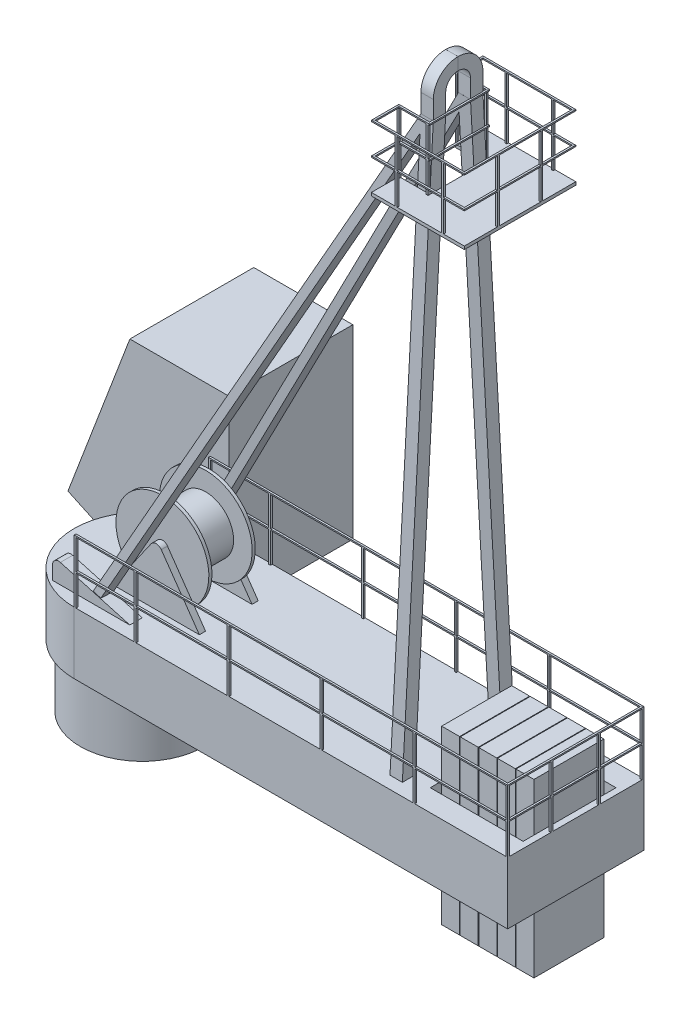
SolidWorks part; units mm, degrees
ref_plane "Front Plane" through (0, 0, 0) normal (0, 0, 1) x (1, 0, 0)
ref_plane "Top Plane" through (0, 0, 0) normal (0, 1, 0) x (1, 0, 0)
ref_plane "Right Plane" through (0, 0, 0) normal (1, 0, 0) x (0, 0, -1)
sketch "Sketch1" plane through (0, 0, 0) normal (0, 1, 0) x (1, 0, 0)
  circle A0 centre (0, 0) radius 1000
  dimension "D1" = 2000
extrude "Boss-Extrude1" add sketch "Sketch1" along normal blind 1000
sketch "Sketch2" plane through (0, 1000, 0) normal (0, 1, 0) x (1, 0, 0)
  line L1 (7000, -1100) -> (0, -1100)
  line L2 (7000, -1100) -> (7000, 1100)
  line L3 (7000, 1100) -> (0, 1100)
  line L5 (5400, -750) -> (6900, -750)
  line L6 (5400, -750) -> (5400, 750)
  line L7 (5400, 750) -> (6900, 750)
  line L8 (6900, -750) -> (6900, 750)
  line L9 (5400, -750) -> (6900, 750) construction
  line L10 (5400, 750) -> (6900, -750) construction
  circle A2 centre (0, 0) radius 1100
  arc A3 (0, 1100) -> (0, -1100) centre (0, 0) ccw
  point P0 (1484.5007, 0)
  point P6 (6150, 0)
  dimension "D2" = 7000
  dimension "D3" = 7000
  dimension "D4" = 1500
  dimension "D5" = 1500
  dimension "D6" = 100
extrude "Boss-Extrude2" add sketch "Sketch2" along normal blind 1000
sketch "Sketch3" plane through (5400, 0, 0) normal (1, 0, 0) x (0, 0, -1)
  line L1 (-565.5574, -8.1645) -> (565.5574, -8.1645)
  line L2 (-565.5574, -8.1645) -> (-565.5574, 2768.8659)
  line L3 (-565.5574, 2768.8659) -> (565.5574, 2768.8659)
  line L4 (565.5574, -8.1645) -> (565.5574, 2768.8659)
  line L5 (-565.5574, -8.1645) -> (565.5574, 2768.8659) construction
  line L6 (-565.5574, 2768.8659) -> (565.5574, -8.1645) construction
  point P0 (0, 1380.3507)
extrude "Boss-Extrude3" add sketch "Sketch3" along normal blind 290 separate body
pattern_linear "LPattern1" count 5 spacing 300 along (1, 0, 0) of "Boss-Extrude3"
ref_plane "Plane1" through (4900, 0, 0) normal (1, 0, 0) x (0, 0, -1)
sketch "Sketch4" plane through (4900, 0, 0) normal (1, 0, 0) x (0, 0, -1)
  line L0 (-900, 2000) -> (-400.308, 11000)
  line L1 (-400.308, 11000) -> (-200, 11000)
  line L2 (-200, 11000) -> (-699.692, 2000)
  line L3 (-1100, 2000) -> (1100, 2000) construction
  line L4 (-699.692, 2000) -> (-900, 2000)
  line L5 (-400.308, 11000) -> (-400.308, 11300)
  line L6 (-200.308, 11000) -> (-200.308, 11300)
  line L7 (-0.157, 11700.151) -> (-0.157, 11500.151)
  line L8 (-1100, 2000) -> (-1100, 1000) construction
  arc A0 (-400.308, 11300) -> (-0.157, 11700.151) centre (-0.157, 11300) cw
  arc A1 (-200.308, 11300) -> (-0.157, 11500.151) centre (-0.157, 11300) cw
  dimension "D1" = 9000
  dimension "D2" = 200
  dimension "D3" = 200
  dimension "D5" = 300
  dimension "D6" = 200
  dimension "D4" = 200
extrude "Boss-Extrude4" add sketch "Sketch4" along normal blind 200 contours L6 A1 L7 A0 L5 L1 | L4 L2 L1 L0 region at (4900, 6500, 550) region at (4900, 11362.768, 237.9729)
ref_plane "Plane2" through (0, 55.9619, 1007.9356) normal (0, 0.0554, 0.9985) x (1, 0, 0)
sketch "Sketch5" plane through (0, 55.9619, 1007.9356) normal (0, 0.0554, 0.9985) x (1, 0, 0)
  line L0 (0, 1935.9449) -> (4900, 10960.8932)
  line L1 (4900, 10960.8932) -> (4900, 10693.5077)
  line L2 (4900, 10693.5077) -> (145.1742, 1935.9449)
  line L3 (145.1742, 1935.9449) -> (0, 1935.9449)
  line L15 (0, 1935.9449) -> (0, 937.4827) construction
  line L18 (0, 1935.9449) -> (7000, 1935.9449) construction
  line L19 (4900, 1947.0321) -> (4900, 10960.8932) construction
extrude "Boss-Extrude6" add sketch "Sketch5" against normal blind 200
ref_plane "Plane3" through (0, 2800, 0) normal (0, 1, 0) x (1, 0, 0)
sketch "Sketch6" plane through (0, 2800, 0) normal (0, 1, 0) x (1, 0, 0)
  line L0 (700, 375) -> (700, -375)
  line L1 (700, -375) -> (1450, -375)
  line L2 (1450, -375) -> (1450, -325)
  line L3 (1450, -325) -> (1150, -325)
  line L4 (1150, -325) -> (1150, 325)
  line L5 (1150, 325) -> (1450, 325)
  line L6 (1450, 325) -> (1450, 375)
  line L7 (1450, 375) -> (700, 375)
  point P2 (700, 0)
  dimension "D1" = 700
  dimension "D2" = 750
  dimension "D3" = 750
  dimension "D4" = 300
  dimension "D5" = 750
  dimension "D6" = 50
  dimension "D7" = 50
revolve "Revolve1" add sketch "Sketch6" angle 360 about L0
sketch "Sketch7" plane through (0, 0, 375) normal (0, 0, 1) x (1, 0, 0)
  line L0 (0, 2000) -> (617.8994, 2882.7134)
  line L1 (781.8621, 2882.5469) -> (1396.9772, 2000)
  line L2 (0, 2000) -> (7000, 2000) construction
  line L3 (0, 2000) -> (1396.9772, 2000)
  arc A1 (781.8621, 2882.5469) -> (617.8994, 2882.7134) centre (699.8226, 2825.3672) ccw
  point P12 (700, 3000)
  dimension "D2" = 1218.9246
  dimension "D3" = 100
  dimension "D1" = 1000
extrude "Boss-Extrude7" add sketch "Sketch7" along normal blind 100
ref_plane "Plane4" through (0, 0, 900) normal (0, 0, 1) x (1, 0, 0)
sketch "Sketch8" plane through (0, 0, 900) normal (0, 0, 1) x (1, 0, 0)
  line L0 (-550, 2000) -> (-550, 2218.1109)
  line L1 (0, 2000) -> (-1100, 2000) construction
  line L2 (-423.0067, 2314.3988) -> (698.4886, 2000)
  line L3 (0, 2000) -> (1396.9772, 2000) construction
  line L4 (-550, 2000) -> (698.4886, 2000)
  arc A0 (-423.0067, 2314.3988) -> (-550, 2218.1109) centre (-450, 2218.1109) ccw
  point P10 (-550, 2350)
  dimension "D2" = 100
  dimension "D1" = 350
extrude "Boss-Extrude8" add sketch "Sketch8" against normal blind 200
mirror "Mirror1" about plane through (0, 0, 0) normal (0, 0, 1) of "Boss-Extrude8", "Boss-Extrude6", "Boss-Extrude4", "Boss-Extrude7"
ref_plane "Plane5" through (0, 10000, 0) normal (0, 1, 0) x (1, 0, 0)
sketch "Sketch9" plane through (0, 10000, 0) normal (0, 1, 0) x (1, 0, 0)
  line L0 (5100, -455.8294) -> (4600, -455.8294)
  line L2 (4600, -455.8294) -> (4600, -900)
  line L3 (-1210, -900) -> (1210, -900) construction
  line L4 (4600, -900) -> (6100, -900)
  line L5 (6100, -900) -> (6100, 900)
  line L6 (6100, 900) -> (4600, 900)
  line L7 (4600, 900) -> (4600, 455.8294)
  line L8 (4600, 455.8294) -> (5100, 455.8294)
  line L10 (5100, 455.8294) -> (5100, -455.8294)
  dimension "D1" = 1000
  dimension "D2" = 500
  dimension "D3" = 500
extrude "Boss-Extrude9" add sketch "Sketch9" against normal blind 50
sketch "Sketch10" plane through (0, 10000, 0) normal (0, 1, 0) x (1, 0, 0)
  line L0 (6100, -900) -> (6100, 900) construction
  line L1 (6070, -365) -> (6100, -365)
  line L2 (6070, -365) -> (6070, -335)
  line L3 (6070, -335) -> (6100, -335)
  line L4 (6100, -365) -> (6100, -335)
  line L5 (6070, -365) -> (6100, -335) construction
  line L6 (6070, -335) -> (6100, -365) construction
  line L7 (4600, -900) -> (6100, -900) construction
  line L8 (5765, -870) -> (5735, -870)
  line L9 (5765, -870) -> (5765, -900)
  line L10 (5765, -900) -> (5735, -900)
  line L11 (5735, -870) -> (5735, -900)
  line L12 (5765, -870) -> (5735, -900) construction
  line L13 (5765, -900) -> (5735, -870) construction
  line L19 (-4455, 0) -> (4455, 0) construction
  line L20 (5015, -870) -> (4985, -870)
  line L21 (5015, -870) -> (5015, -900)
  line L22 (5015, -900) -> (4985, -900)
  line L23 (4985, -870) -> (4985, -900)
  line L24 (5015, -870) -> (4985, -900) construction
  line L25 (5015, -900) -> (4985, -870) construction
  line L26 (5015, 900) -> (4985, 870) construction
  line L27 (5015, 870) -> (4985, 900) construction
  line L28 (5765, 900) -> (5735, 870) construction
  line L29 (5765, 870) -> (5735, 900) construction
  line L30 (6070, 335) -> (6100, 365) construction
  line L31 (6070, 365) -> (6100, 335) construction
  line L32 (4985, 870) -> (4985, 900)
  line L33 (5015, 900) -> (4985, 900)
  line L34 (5015, 870) -> (5015, 900)
  line L35 (5015, 870) -> (4985, 870)
  line L36 (5735, 870) -> (5735, 900)
  line L37 (5765, 900) -> (5735, 900)
  line L38 (5765, 870) -> (5765, 900)
  line L39 (5765, 870) -> (5735, 870)
  line L40 (6100, 365) -> (6100, 335)
  line L41 (6070, 335) -> (6100, 335)
  line L42 (6070, 365) -> (6070, 335)
  line L43 (6070, 365) -> (6100, 365)
  line L44 (5070, 455.8294) -> (5100, 485.8294) construction
  line L45 (4630, -485.8294) -> (4600, -485.8294)
  line L46 (4630, -485.8294) -> (4630, -455.8294)
  line L47 (4630, -455.8294) -> (4600, -455.8294)
  line L48 (4600, -485.8294) -> (4600, -455.8294)
  line L49 (4630, -485.8294) -> (4600, -455.8294) construction
  line L50 (4630, -455.8294) -> (4600, -485.8294) construction
  line L51 (5070, -485.8294) -> (5100, -485.8294)
  line L52 (5070, -485.8294) -> (5070, -455.8294)
  line L53 (5070, -455.8294) -> (5100, -455.8294)
  line L54 (5100, -485.8294) -> (5100, -455.8294)
  line L55 (5070, -485.8294) -> (5100, -455.8294) construction
  line L56 (5070, -455.8294) -> (5100, -485.8294) construction
  line L57 (5070, 485.8294) -> (5100, 455.8294) construction
  line L58 (4630, 455.8294) -> (4600, 485.8294) construction
  line L59 (4630, 485.8294) -> (4600, 455.8294) construction
  line L60 (5100, 485.8294) -> (5100, 455.8294)
  line L61 (5070, 455.8294) -> (5100, 455.8294)
  line L62 (5070, 485.8294) -> (5070, 455.8294)
  line L63 (5070, 485.8294) -> (5100, 485.8294)
  line L64 (4600, 485.8294) -> (4600, 455.8294)
  line L65 (4630, 455.8294) -> (4600, 455.8294)
  line L66 (4630, 485.8294) -> (4630, 455.8294)
  line L67 (4630, 485.8294) -> (4600, 485.8294)
  point P0 (6085, -350)
  point P7 (5750, -885)
  point P14 (5000, -885)
  point P34 (5000, 885)
  point P35 (5750, 885)
  point P36 (6085, 350)
  point P37 (4615, -470.8294)
  point P43 (5085, -470.8294)
  point P57 (5085, 470.8294)
  point P58 (4615, 470.8294)
  dimension "D1" = 30
  dimension "D2" = 30
  dimension "D3" = 30
  dimension "D4" = 30
  dimension "D5" = 30
  dimension "D6" = 30
  dimension "D7" = 350
  dimension "D8" = 350
  dimension "D9" = 750
  dimension "D10" = 30
  dimension "D11" = 30
  dimension "D12" = 30
  dimension "D13" = 30
extrude "Boss-Extrude10" add sketch "Sketch10" along normal blind 1000
sketch "Sketch11" plane through (0, 11000, 0) normal (0, 1, 0) x (1, 0, 0)
  line L0 (5110, -470.8294) -> (4615, -470.8294)
  line L3 (4615, -470.8294) -> (4615, -885)
  line L5 (4615, -885) -> (6085, -885)
  line L6 (6085, -885) -> (6085, 885)
  line L7 (6085, 885) -> (4615, 885)
  line L8 (4615, 885) -> (4615, 470.8294)
  line L9 (4615, 470.8294) -> (5110, 470.8294)
  line L10 (5110, 470.8294) -> (5110, -470.8294)
  line L11 (4985, 900) -> (4985, 870) construction
  line L12 (4630, 485.8294) -> (4600, 485.8294) construction
  line L14 (5070, 485.8294) -> (5070, 455.8294) construction
  line L16 (4630, -485.8294) -> (4630, -455.8294) construction
  line L17 (4600, -485.8294) -> (4630, -485.8294) construction
  line L19 (5015, -900) -> (5015, -870) construction
  line L20 (6070, -365) -> (6100, -365) construction
  line L21 (5100, -485.8294) -> (5100, -455.8294) construction
  point P5 (4630, -470.8294)
  point P22 (4985, 885)
  point P26 (4615, 485.8294)
  point P29 (5070, 470.8294)
  point P32 (4615, -485.8294)
  point P33 (5015, -885)
  point P36 (6085, -365)
  dimension "D1" = 10
sketch "Sketch19" plane through (0, 0, 485.8294) normal (0, 0, 1) x (1, 0, 0)
  line L0 (4600, 11000) -> (4630, 11000) construction
  line L1 (4600, 11010) -> (4630, 11010)
  line L2 (4600, 11010) -> (4600, 10990)
  line L3 (4600, 10990) -> (4630, 10990)
  line L4 (4630, 11010) -> (4630, 10990)
  line L5 (4600, 11010) -> (4630, 10990) construction
  line L6 (4600, 10990) -> (4630, 11010) construction
  line L7 (4630, 11000) -> (4630, 10000) construction
  point P0 (4615, 11000)
  dimension "D1" = 20
sweep "Sweep3" add profiles "Sketch19" path "Sketch11"
sketch "Sketch20" plane through (0, 2000, 0) normal (0, 1, 0) x (1, 0, 0)
  line L0 (5470, -1070) -> (5470, -1100)
  line L1 (6970, -1070) -> (7000, -1070)
  line L2 (6970, -1070) -> (6970, -1100)
  line L3 (6970, -1100) -> (7000, -1100)
  line L4 (7000, -1070) -> (7000, -1100)
  line L5 (6970, -1070) -> (7000, -1100) construction
  line L6 (6970, -1100) -> (7000, -1070) construction
  line L7 (5470, -1070) -> (5500, -1070)
  line L8 (5500, -1070) -> (5500, -1100)
  line L9 (5470, -1100) -> (5500, -1100)
  line L10 (3970, -1070) -> (3970, -1100)
  line L11 (3970, -1070) -> (4000, -1070)
  line L12 (4000, -1070) -> (4000, -1100)
  line L13 (3970, -1100) -> (4000, -1100)
  line L14 (2470, -1070) -> (2470, -1100)
  line L15 (2470, -1070) -> (2500, -1070)
  line L16 (2500, -1070) -> (2500, -1100)
  line L17 (2470, -1100) -> (2500, -1100)
  line L18 (970, -1070) -> (970, -1100)
  line L19 (970, -1070) -> (1000, -1070)
  line L20 (1000, -1070) -> (1000, -1100)
  line L21 (970, -1100) -> (1000, -1100)
  line L22 (6970, -370) -> (6970, -400)
  line L23 (30, -1070) -> (0, -1070)
  line L24 (30, -1070) -> (30, -1100)
  line L25 (30, -1100) -> (0, -1100)
  line L26 (0, -1070) -> (0, -1100)
  line L27 (30, -1070) -> (0, -1100) construction
  line L28 (30, -1100) -> (0, -1070) construction
  line L29 (6970, -370) -> (7000, -370)
  line L30 (7000, -370) -> (7000, -400)
  line L31 (6970, -400) -> (7000, -400)
  line L33 (-4455, 0) -> (4455, 0) construction
  line L34 (30, 1100) -> (0, 1070) construction
  line L35 (30, 1070) -> (0, 1100) construction
  line L36 (6970, 1100) -> (7000, 1070) construction
  line L37 (6970, 1070) -> (7000, 1100) construction
  line L38 (6970, 400) -> (7000, 400)
  line L39 (7000, 370) -> (7000, 400)
  line L40 (6970, 370) -> (7000, 370)
  line L41 (0, 1070) -> (0, 1100)
  line L42 (30, 1100) -> (0, 1100)
  line L43 (30, 1070) -> (30, 1100)
  line L44 (30, 1070) -> (0, 1070)
  line L45 (6970, 370) -> (6970, 400)
  line L46 (970, 1100) -> (1000, 1100)
  line L47 (1000, 1070) -> (1000, 1100)
  line L48 (970, 1070) -> (1000, 1070)
  line L49 (970, 1070) -> (970, 1100)
  line L50 (2470, 1100) -> (2500, 1100)
  line L51 (2500, 1070) -> (2500, 1100)
  line L52 (2470, 1070) -> (2500, 1070)
  line L53 (2470, 1070) -> (2470, 1100)
  line L54 (3970, 1100) -> (4000, 1100)
  line L55 (4000, 1070) -> (4000, 1100)
  line L56 (3970, 1070) -> (4000, 1070)
  line L57 (3970, 1070) -> (3970, 1100)
  line L58 (5470, 1100) -> (5500, 1100)
  line L59 (5500, 1070) -> (5500, 1100)
  line L60 (5470, 1070) -> (5500, 1070)
  line L61 (5470, 1070) -> (5470, 1100)
  line L62 (6970, 1100) -> (7000, 1100)
  line L63 (7000, 1070) -> (7000, 1100)
  line L64 (6970, 1070) -> (7000, 1070)
  line L65 (6970, 1070) -> (6970, 1100)
  point P0 (6985, -1085)
  point P6 (15, -1085)
  point P64 (15, 1085)
  point P65 (6985, 1085)
  dimension "D1" = 30
  dimension "D2" = 30
  dimension "D4" = 30
  dimension "D5" = 30
  dimension "D3" = 5
  dimension "D6" = 2
extrude "Boss-Extrude11" add sketch "Sketch20" along normal blind 1000
pattern_linear "LPattern2" count 2 spacing 500 along (0, -1, 0) of "Sweep3"
sketch "Sketch21" plane through (0, 3000, 0) normal (0, 1, 0) x (1, 0, 0)
  line L0 (0, -1085) -> (6985, -1085)
  line L1 (0, -1070) -> (0, -1100) construction
  line L2 (6985, -1085) -> (6985, 1085)
  line L3 (6985, 1085) -> (0, 1085)
  line L4 (0, 1100) -> (0, 1070) construction
sketch "Sketch22" plane through (0, 0, 0) normal (-1, 0, 0) x (0, 0, 1)
  line L0 (1100, 3000) -> (1100, 2000) construction
  line L1 (1070, 3010) -> (1100, 3010)
  line L2 (1070, 3010) -> (1070, 2990)
  line L3 (1070, 2990) -> (1100, 2990)
  line L4 (1100, 3010) -> (1100, 2990)
  line L5 (1070, 3010) -> (1100, 2990) construction
  line L6 (1070, 2990) -> (1100, 3010) construction
  point P0 (1085, 3000)
  dimension "D1" = 20
sweep "Sweep4" add profiles "Sketch22" path "Sketch21"
pattern_linear "LPattern3" count 2 spacing 500 along (0, -1, 0) of "Sweep4"
ref_plane "Plane6" through (0, 0, 0) normal (1, 0, 0) x (0, 0, -1)
sketch "Sketch23" plane through (0, 0, 0) normal (1, 0, 0) x (0, 0, -1)
  line L0 (-1100, 1000) -> (1100, 1000) construction
  line L1 (3100, 4000) -> (1100, 4000)
  line L2 (3100, 4000) -> (3100, 1000)
  line L3 (3100, 1000) -> (1100, 1000)
  line L4 (1100, 4000) -> (1100, 1000)
  line L5 (3100, 4000) -> (1100, 1000) construction
  line L6 (3100, 1000) -> (1100, 4000) construction
  line L7 (1100, 2000) -> (1100, 1000) construction
  point P0 (2100, 2500)
  dimension "D1" = 3000
  dimension "D2" = 2000
extrude "Boss-Extrude12" add sketch "Sketch23" along normal mid plane 600
sketch "Sketch24" plane through (0, 0, -3100) normal (0, 0, -1) x (-1, 0, 0)
  line L0 (300, 4000) -> (1300, 4000)
  line L1 (1300, 4000) -> (2300, 1373.0461)
  line L2 (2300, 1373.0461) -> (1500, 1000)
  line L3 (1500, 1000) -> (300, 1000)
  line L4 (300, 1000) -> (300, 4000)
  dimension "D1" = 1000
  dimension "D2" = 1200
  dimension "D3" = 2000
  dimension "D4" = 25
extrude "Boss-Extrude13" add sketch "Sketch24" along direction (0, 0, -1) on the side against the normal up to vertex (2000 mm away) up to point (-300, 4000, -1100)
equation "\"D3@Sketch2\"=\"D2@Sketch2\""
equation "\"D3@Sketch6\"=\"D2@Sketch6\""
equation "\"D7@Sketch6\"=\"D6@Sketch6\""
equation "\"D3@Sketch9\"=\"D2@Sketch9\""
equation "\"D2@Sketch10\"=\"D1@Sketch10\""
equation "\"D3@Sketch10\"=\"D1@Sketch10\""
equation "\"D4@Sketch10\"=\"D1@Sketch10\""
equation "\"D5@Sketch10\"=\"D1@Sketch10\""
equation "\"D6@Sketch10\"=\"D1@Sketch10\""
equation "\"D10@Sketch10\"=\"D1@Sketch10\""
equation "\"D11@Sketch10\"=\"D1@Sketch10\""
equation "\"D12@Sketch10\"=\"D1@Sketch10\""
equation "\"D13@Sketch10\"=\"D1@Sketch10\""
